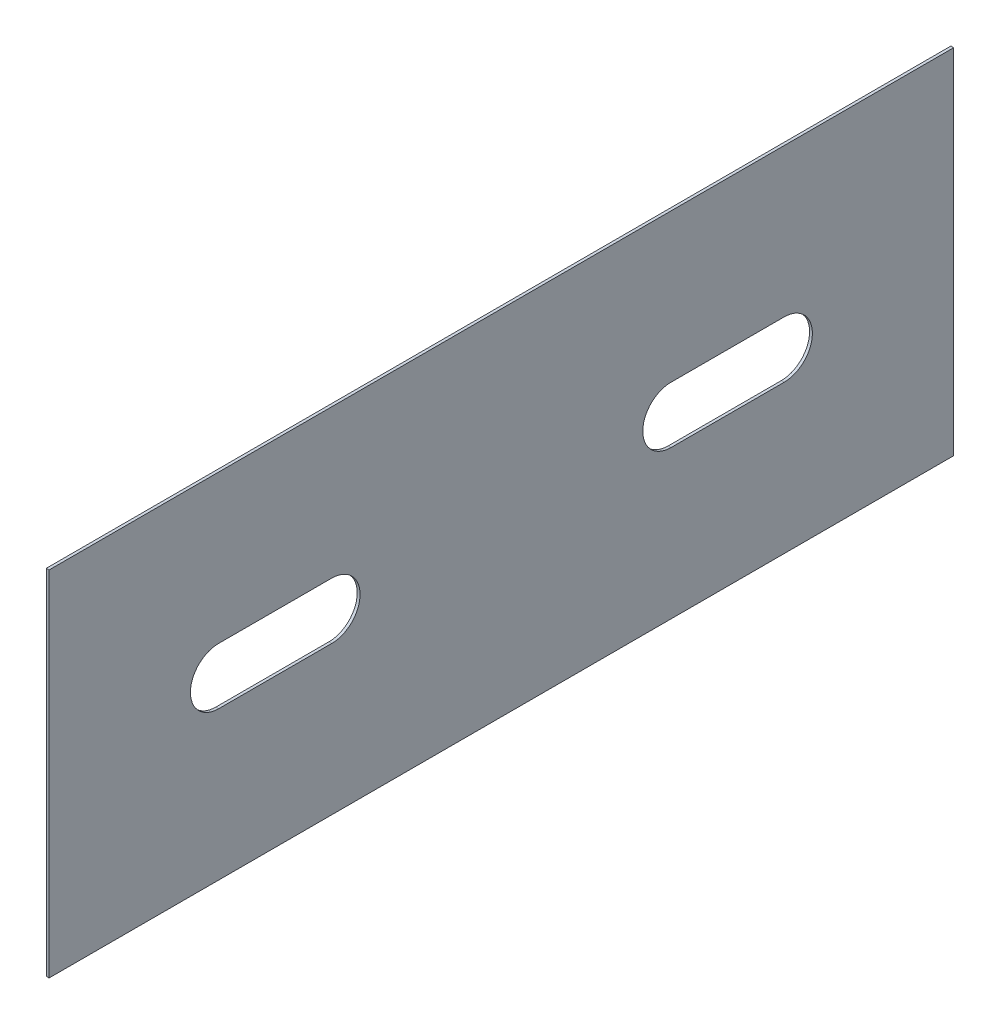
SolidWorks part; units mm, degrees
ref_plane "Front Plane" through (0, 0, 0) normal (0, 0, 1) x (1, 0, 0)
ref_plane "Top Plane" through (0, 0, 0) normal (0, 1, 0) x (1, 0, 0)
ref_plane "Right Plane" through (0, 0, 0) normal (1, 0, 0) x (0, 0, -1)
sketch "Sketch1" plane through (0, 0, 0) normal (1, 0, 0) x (0, 0, -1)
  line L0 (1.2451, 135.7198) -> (1.2451, -114.2802) construction
  line L1 (-318.7549, 135.7198) -> (321.2451, 135.7198)
  line L2 (-318.7549, 135.7198) -> (-318.7549, -114.2802)
  line L3 (-318.7549, -114.2802) -> (321.2451, -114.2802)
  line L4 (321.2451, 135.7198) -> (321.2451, -114.2802)
  line L5 (1.2451, 10.7198) -> (-318.7549, 10.7198) construction
  line L6 (-158.7549, 10.7198) -> (-158.7549, 135.7198) construction
  line L7 (1.2451, 10.7198) -> (321.2451, 10.7198) construction
  line L8 (161.2451, 10.7198) -> (161.2451, 135.7198) construction
  line L9 (-198.7549, 10.7198) -> (-118.7549, 10.7198) construction
  line L10 (-198.7549, 30.7198) -> (-118.7549, 30.7198)
  line L11 (-198.7549, -9.2802) -> (-118.7549, -9.2802)
  line L12 (201.2451, 10.7198) -> (121.2451, 10.7198) construction
  line L13 (201.2451, 10.7198) -> (121.2451, 10.7198) construction
  line L14 (201.2451, 10.7198) -> (121.2451, 10.7198) construction
  line L15 (121.2451, 10.7198) -> (201.2451, 10.7198) construction
  line L16 (121.2451, 30.7198) -> (201.2451, 30.7198)
  line L17 (121.2451, -9.2802) -> (201.2451, -9.2802)
  arc A0 (-198.7549, 30.7198) -> (-198.7549, -9.2802) centre (-198.7549, 10.7198) ccw
  arc A1 (-118.7549, -9.2802) -> (-118.7549, 30.7198) centre (-118.7549, 10.7198) ccw
  arc A2 (121.2451, 30.7198) -> (121.2451, -9.2802) centre (121.2451, 10.7198) ccw
  arc A3 (201.2451, -9.2802) -> (201.2451, 30.7198) centre (201.2451, 10.7198) ccw
  point P15 (-158.7549, 10.7198)
  point P22 (161.2451, 10.7198)
  dimension "D3" = 40
  dimension "D5" = 20
  dimension "D6" = 20
  dimension "D1" = 640
  dimension "D2" = 250
  dimension "D4" = 40
extrude "Boss-Extrude1" add sketch "Sketch1" along normal blind 2
